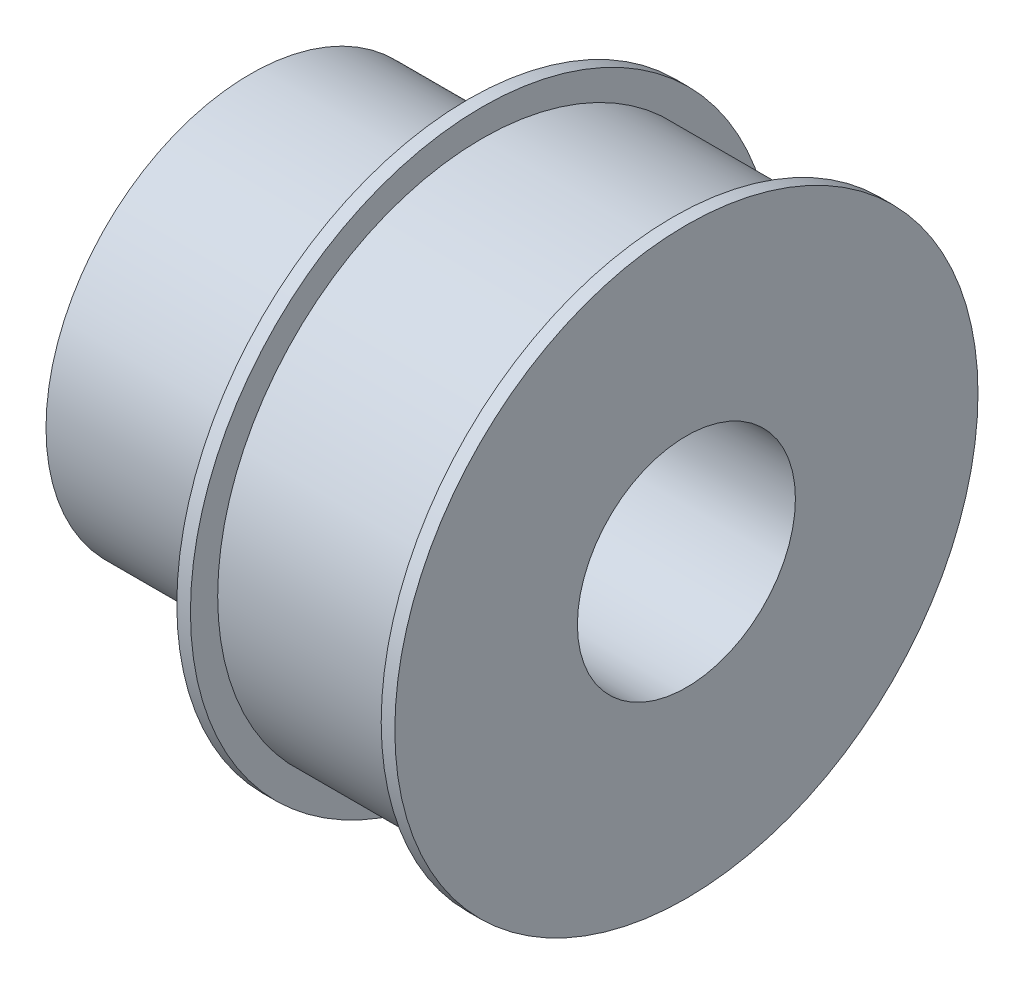
SolidWorks part; units mm, degrees
ref_plane "前视基准面" through (0, 0, 0) normal (0, 0, 1) x (1, 0, 0)
ref_plane "上视基准面" through (0, 0, 0) normal (0, 1, 0) x (1, 0, 0)
ref_plane "右视基准面" through (0, 0, 0) normal (1, 0, 0) x (0, 0, -1)
sketch "草图1" plane through (0, 0, 0) normal (1, 0, 0) x (0, 0, -1)
  circle A0 centre (0, 0) radius 9.7
  dimension "D1" = 19.4
extrude "凸台-拉伸1" add sketch "草图1" along normal blind 7
sketch "草图2" plane through (0, 0, 0) normal (-1, 0, 0) x (0, 0, 1)
  circle A0 centre (0, 0) radius 10.7
  circle A1 centre (0, 0) radius 9.7 construction
  dimension "D1" = 1
extrude "凸台-拉伸2" add sketch "草图2" along normal blind 0.5
sketch "草图3" plane through (7, 0, 0) normal (1, 0, 0) x (0, 0, -1)
  circle A0 centre (0, 0) radius 10.7
extrude "凸台-拉伸3" add sketch "草图3" along normal blind 0.5
sketch "草图4" plane through (-0.5, 0, 0) normal (-1, 0, 0) x (0, 0, 1)
  circle A0 centre (0, 0) radius 4
  dimension "D1" = 8
extrude "切除-拉伸1" cut sketch "草图4" against normal blind 14.5
sketch "草图5" plane through (-0.5, 0, 0) normal (-1, 0, 0) x (0, 0, 1)
  circle A0 centre (0, 0) radius 4 construction
  circle A1 centre (0, 0) radius 4
  circle A2 centre (0, 0) radius 7.5
  dimension "D1" = 15
extrude "凸台-拉伸4" add sketch "草图5" along normal offset from surface (8 mm away) 16 up to face at (7.5, 0, -4)
